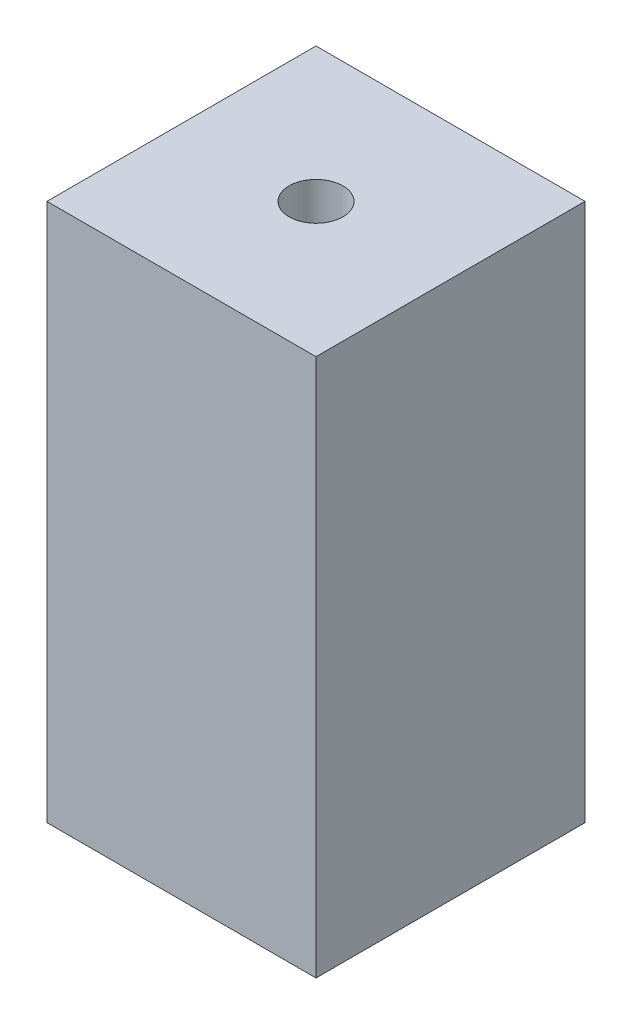
SolidWorks part; units mm, degrees
ref_plane "Front Plane" through (0, 0, 0) normal (0, 0, 1) x (1, 0, 0)
ref_plane "Top Plane" through (0, 0, 0) normal (0, 1, 0) x (1, 0, 0)
ref_plane "Right Plane" through (0, 0, 0) normal (1, 0, 0) x (0, 0, -1)
sketch "Sketch1" plane through (0, 0, 0) normal (0, 1, 0) x (1, 0, 0)
  line L0 (0, -8.25) -> (0, 8.25) construction
  line L1 (-7.5, 7.5) -> (7.5, 7.5)
  line L2 (-7.5, 7.5) -> (-7.5, -7.5)
  line L3 (-7.5, -7.5) -> (7.5, -7.5)
  line L4 (7.5, 7.5) -> (7.5, -7.5)
  line L5 (-8.25, 0) -> (8.25, 0) construction
  circle A0 centre (0, 0) radius 1.5
  dimension "D5" = 3
  dimension "D1" = 15
  dimension "D2" = 15
  dimension "D3" = 7.5
  dimension "D4" = 7.5
extrude "Boss-Extrude1" add sketch "Sketch1" along normal blind 30
